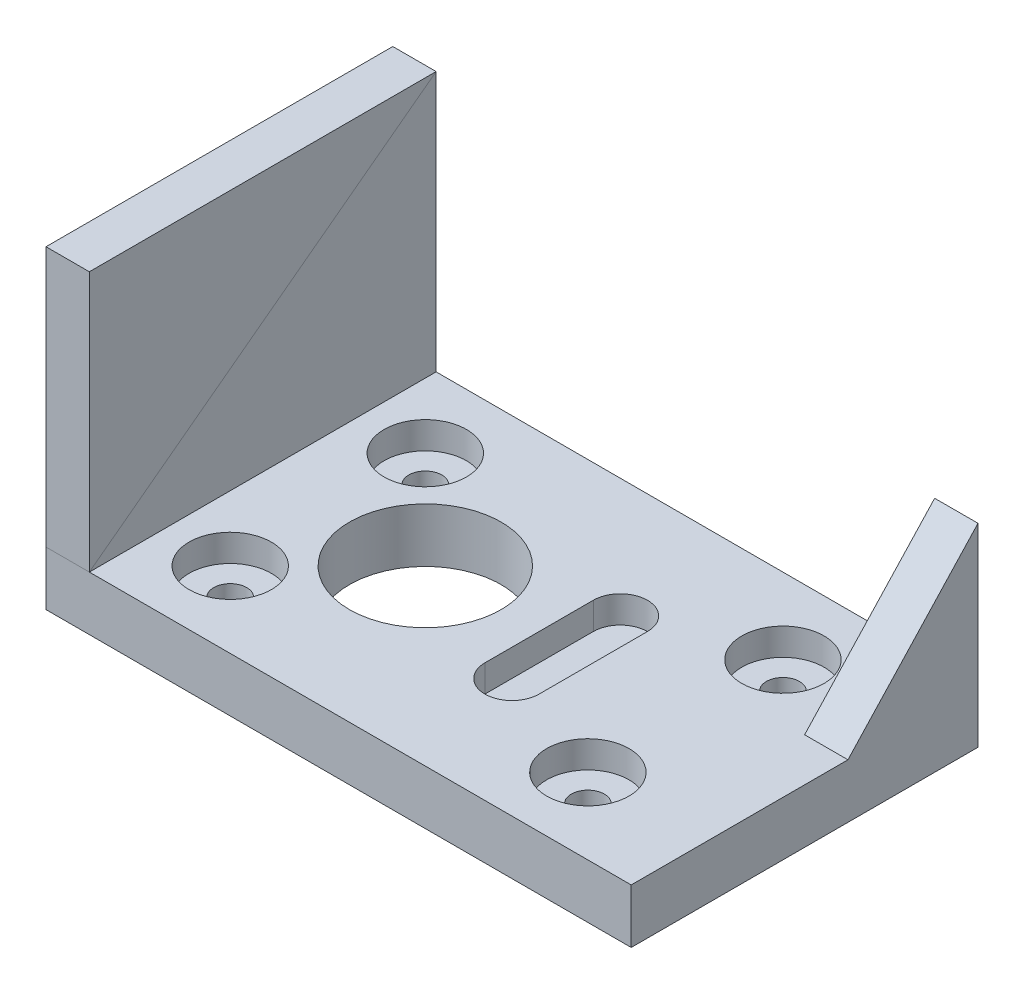
SolidWorks part; units mm, degrees
ref_plane "Front" through (0, 0, 0) normal (0, 0, 1) x (1, 0, 0)
ref_plane "Top" through (0, 0, 0) normal (0, 1, 0) x (1, 0, 0)
ref_plane "Right" through (0, 0, 0) normal (1, 0, 0) x (0, 0, -1)
sketch "Sketch2" plane through (0, 0, 0) normal (0, 1, 0) x (1, 0, 0)
  line L1 (-23, -16) -> (23, -16)
  line L2 (-23, -16) -> (-23, 16)
  line L3 (-23, 16) -> (23, 16)
  line L4 (23, -16) -> (23, 16)
  line L5 (-23, -16) -> (23, 16) construction
  line L6 (-23, 16) -> (23, -16) construction
  circle A0 centre (-17, 9) radius 1.525
  circle A1 centre (-17, -9) radius 1.525
  circle A2 centre (16, -9) radius 1.525
  circle A3 centre (16, 9) radius 1.525
  circle A4 centre (-8, 0) radius 7
  point P0 (0, 0)
  dimension "D3" = 3.05
  dimension "D4" = 7
  dimension "D5" = 6
  dimension "D6" = 7
  dimension "D7" = 7
  dimension "D8" = 7
  dimension "D9" = 7
  dimension "D10" = 7
  dimension "D11" = 6
  dimension "D12" = 14
  dimension "D13" = 15
  dimension "D14" = 16
  dimension "D1" = 46
  dimension "D2" = 32
extrude "Boss-Extrude1" add sketch "Sketch2" along normal blind 5
sketch "Sketch3" plane through (0, 5, 0) normal (0, 1, 0) x (1, 0, 0)
  line L0 (5, 5) -> (5, -5) construction
  line L1 (7.5, 5) -> (7.5, -5)
  line L2 (2.5, 5) -> (2.5, -5)
  line L3 (-23, -16) -> (23, -16) construction
  line L4 (-23, 16) -> (-23, -16) construction
  circle A0 centre (-17, 9) radius 3.8
  circle A1 centre (-17, -9) radius 3.8
  circle A2 centre (16, -9) radius 3.8
  circle A3 centre (16, 9) radius 3.8
  arc A4 (7.5, 5) -> (2.5, 5) centre (5, 5) ccw
  arc A5 (2.5, -5) -> (7.5, -5) centre (5, -5) ccw
  point P14 (5, 0)
  dimension "D1" = 7.6
  dimension "D3" = 2.5
  dimension "D2" = 10
  dimension "D4" = 11
  dimension "D5" = 28
extrude "Cut-Extrude1" cut sketch "Sketch3" against normal blind 2.5
sketch "Sketch4" plane through (0, 0, 0) normal (0, -1, 0) x (-1, 0, 0)
  line L3 (23, 16) -> (-23, 16)
  line L5 (27, 18.5) -> (-27, 18.5)
  line L6 (27, 18.5) -> (27, -16)
  line L7 (27, -16) -> (23, -16)
  line L8 (23, 16) -> (23, -16) construction
  line L9 (23, -16) -> (23, 16)
  line L10 (-27, 18.5) -> (-27, -16)
  line L11 (-27, -16) -> (-23, -16)
  line L13 (-23, -16) -> (-23, 16)
  dimension "D5" = 34.5
  dimension "D6" = 90
extrude "Boss-Extrude2" add sketch "Sketch4" against normal blind 87.8
extrude "Boss-Extrude3" add sketch "Sketch2<2>" against normal blind 5 from surface starting at face at (0, 87.8, -0.625)
sketch "Sketch2<2>" plane through (0, 0, 0) normal (0, 1, 0) x (1, 0, 0) same geometry as "Sketch2"
extrude "Cut-Extrude2" cut sketch "Sketch3<3>" along normal blind 2.5 from surface starting at face at (0, 82.8, 0)
sketch "Sketch3<3>" plane through (0, 5, 0) normal (0, 1, 0) x (1, 0, 0) same geometry as "Sketch3"
sketch "Sketch5" plane through (27, 0, 0) normal (1, 0, 0) x (0, 0, -1)
  line L0 (-16, 0) -> (-16, 5)
  line L1 (-16, 87.8) -> (-16, 0) construction
  line L2 (-16, 5) -> (4, 5)
  line L3 (4, 5) -> (16, 17.9)
  line L4 (16, 17.9) -> (16, 73.9)
  line L5 (16, 73.9) -> (7, 82.8)
  line L6 (7, 82.8) -> (-16, 82.8)
  line L7 (-16, 82.8) -> (-16, 5)
  line L8 (18.5, 87.8) -> (-16, 87.8) construction
  line L9 (18.5, 87.8) -> (18.5, 0) construction
  line L10 (-16, 43.9) -> (18.5, 43.9) construction
  line M8 (-16, 87.8) -> (-16, 0)
  dimension "D1" = 5
  dimension "D2" = 5
  dimension "D3" = 2.5
  dimension "D4" = 26
  dimension "D5" = 30
  dimension "D6" = 20
  dimension "D7" = 23
extrude "Cut-Extrude3" cut sketch "Sketch5" against normal blind 5 contours L10 L7 L2 L3 L4 | L10 L4 L5 L6 M8 region at (27, 25.4545, 0.7956) region at (27, 62.802, 0.4322)
sketch "Sketch6" plane through (-27, 0, 0) normal (-1, 0, 0) x (0, 0, 1)
  line L1 (16, 87.8) -> (16, 0) construction
  line L2 (16, 82.8) -> (16, 5)
  line L3 (-16, 58.8) -> (-16, 29)
  line L5 (16, 82.8) -> (-16, 58.8)
  line L6 (16, 5) -> (-16, 29)
  line L7 (-18.5, 87.8) -> (-18.5, 0) construction
  line L10 (16, 0) -> (-18.5, 0) construction
  line L11 (16, 87.8) -> (-18.5, 87.8) construction
  dimension "D3" = 2.5
  dimension "D4" = 29
  dimension "D5" = 29
extrude "Cut-Extrude4" cut sketch "Sketch6" against normal blind 5
sketch "Sketch7" plane through (27, 0, 0) normal (1, 0, 0) x (0, 0, -1)
  line L0 (16, 45.9) -> (16, 58.8)
  line L1 (16, 17.9) -> (16, 73.9) construction
  line L2 (16, 58.8) -> (-16, 82.8)
  line L3 (-16, 82.8) -> (-16, 87.8)
  line L4 (-16, 87.8) -> (18.5, 87.8)
  line L5 (18.5, 87.8) -> (18.5, 0)
  line L6 (18.5, 0) -> (16, 0)
  line L7 (18.5, 0) -> (-16, 0) construction
  line L8 (16, 0) -> (16, 45.9)
extrude "Cut-Extrude5" cut sketch "Sketch7" against normal blind 66
sketch "Sketch8" plane through (0, 0, -16) normal (0, 0, -1) x (-1, 0, 0)
  line L0 (-27, 17.9) -> (-27, 0) construction
  line L1 (27, 0) -> (-27, 0) construction
  line L2 (27, 0) -> (27, 29) construction
  circle A0 centre (-24.5, 2.5) radius 1.6
  circle A1 centre (7, 2.5) radius 1.6
  circle A2 centre (24.8358, 24.6816) radius 1.6
  circle A3 centre (-25, 13.9909) radius 1.6
  dimension "D1" = 3.2
  dimension "D2" = 2.5
  dimension "D3" = 2.5
  dimension "D4" = 2
  dimension "D5" = 2.5
  dimension "D6" = 20
sketch "Sketch9" plane through (-27, 0, 0) normal (-1, 0, 0) x (0, 0, 1)
  line L0 (16, 5) -> (-16, 29)
  line L1 (-16, 29) -> (16, 29)
  line L2 (16, 29) -> (16, 5)
extrude "Boss-Extrude5" add sketch "Sketch9" against normal blind 4 separate body contours L2 L0 L1
